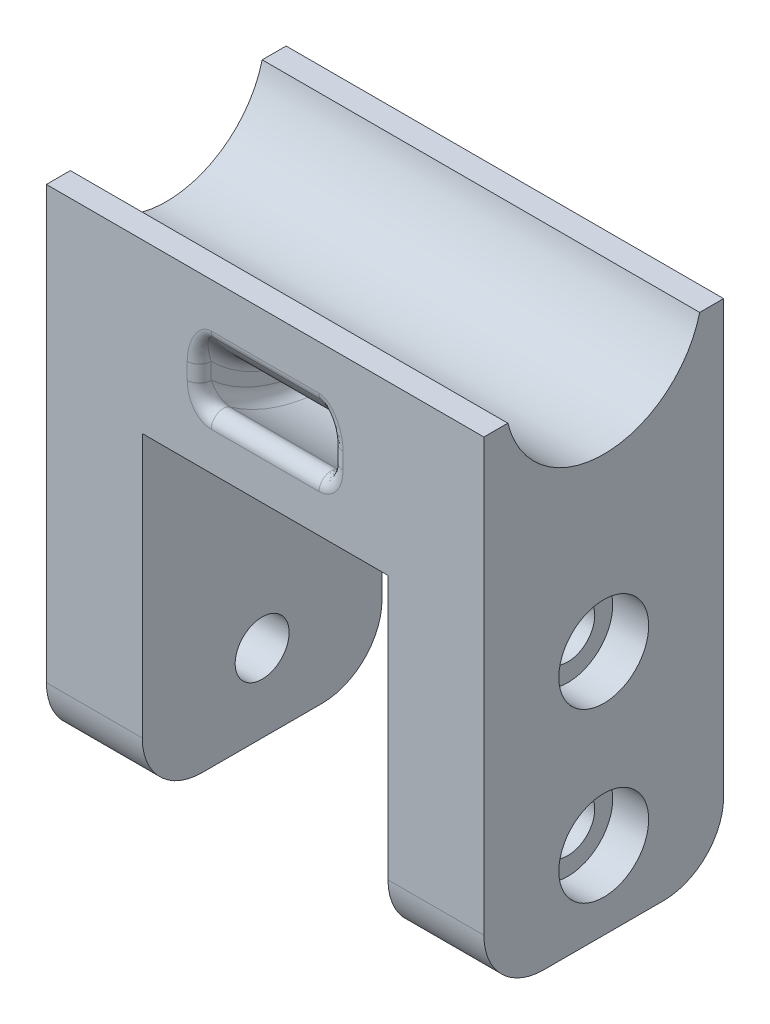
SolidWorks part; units mm, degrees
ref_plane "Спереди" through (0, 0, 0) normal (0, 0, 1) x (1, 0, 0)
ref_plane "Сверху" through (0, 0, 0) normal (0, 1, 0) x (1, 0, 0)
ref_plane "Справа" through (0, 0, 0) normal (1, 0, 0) x (0, 0, -1)
sketch "Эскиз1" plane through (0, 0, 0) normal (0, 1, 0) x (1, 0, 0)
  line L1 (-10, 10) -> (10, 10)
  line L2 (-10, 10) -> (-10, -10)
  line L3 (-10, -10) -> (10, -10)
  line L4 (10, 10) -> (10, -10)
  line L5 (-10, 10) -> (10, -10) construction
  line L6 (-10, -10) -> (10, 10) construction
  point P0 (0, 0)
  dimension "D1" = 20
  dimension "D2" = 20
extrude "Бобышка-Вытянуть1" add sketch "Эскиз1" along normal blind 14
sketch "Эскиз2" plane through (-10, 0, 0) normal (-1, 0, 0) x (0, 0, 1)
  line L0 (-10, 14) -> (10, 14) construction
  circle A0 centre (0, 16) radius 8.25
  dimension "D1" = 16.5
  dimension "D2" = 2
extrude "Вырез-Вытянуть1" cut sketch "Эскиз2" against normal through all
sketch "Эскиз3" plane through (0, 0, 0) normal (1, 0, 0) x (0, 0, -1)
  line L0 (-10, 14) -> (-10, 10) construction
  line L1 (-10, 14) -> (-10, 0) construction
  circle A0 centre (0, 16) radius 11.6619
  circle A1 centre (0, 16) radius 14.6619
  arc A2 (-8.0039, 14) -> (8.0039, 14) centre (0, 16) ccw construction
  dimension "D1" = 4
  dimension "D2" = 3
extrude "Вырез-Вытянуть2" cut sketch "Эскиз3" against normal mid plane 11
fillet "Скругление1" radius 1 12 edges at (0, 5.2775, -10) (5.5, 1.3381, 0) (0, 5.2775, 10) (-5.5, 1.3381, 0) (-5.5, 4.3381, 0) (0, 10, 10) (5.5, 4.3381, 0) (0, 10, -10) (-5.5, 7.6388, 10) (-5.5, 7.6388, -10) (5.5, 7.6388, 10) (5.5, 7.6388, -10)
sketch "Эскиз5" plane through (-10, 0, 0) normal (-1, 0, 0) x (0, 0, 1)
  line L0 (10, 14) -> (10, 0) construction
  line L1 (10, -27) -> (-10, -27)
  line L2 (10, -27) -> (10, 0)
  line L3 (10, 0) -> (-10, 0) construction
  line L4 (-10, -27) -> (-10, 0)
  line L5 (10, -27) -> (-10, 0) construction
  line L6 (10, 0) -> (-10, -27) construction
  line L7 (-10, -13.5) -> (10, -13.5) construction
  line L18 (10, 14) -> (8.0039, 14)
  line L19 (-8.0039, 14) -> (-10, 14)
  line L20 (-10, 14) -> (-10, 0)
  line L21 (-10, 0) -> (10, 0)
  line L22 (10, 0) -> (10, 14)
  line L23 (10, 14) -> (8.0039, 14)
  line L24 (-8.0039, 14) -> (-10, 14)
  line L25 (-10, 14) -> (-10, 0)
  line L26 (-10, 0) -> (10, 0) construction
  line L27 (10, 0) -> (10, 14)
  circle A0 centre (0, -6.5) radius 2.25
  circle A1 centre (0, -20.5) radius 2.25
  arc A4 (-8.0039, 14) -> (8.0039, 14) centre (0, 16) ccw
  arc A5 (-8.0039, 14) -> (8.0039, 14) centre (0, 16) ccw
  point P0 (0, -13.5)
  dimension "D2" = 4.5
  dimension "D1" = 27
  dimension "D3" = 14
  dimension "D4" = 0
extrude "Бобышка-Вытянуть2" add sketch "Эскиз5" along normal blind 8.25
sketch "Эскиз6" plane through (-10, 0, 0) normal (1, 0, 0) x (0, 0, -1)
  line L8 (10, -27) -> (10, 0)
  line L9 (10, 0) -> (-10, 0)
  line L10 (-10, 0) -> (-10, -27)
  line L11 (-10, -27) -> (10, -27)
  line L12 (10, -27) -> (10, 0)
  line L13 (10, 0) -> (-10, 0)
  line L14 (-10, 0) -> (-10, -27)
  line L15 (-10, -27) -> (10, -27)
  dimension "D1" = 0
extrude "Вырез-Вытянуть3" cut sketch "Эскиз6" against normal blind 0.25
sketch "Эскиз7" plane through (-18.25, 0, 0) normal (-1, 0, 0) x (0, 0, 1)
  circle A0 centre (0, -6.5) radius 3.75
  circle A1 centre (0, -20.5) radius 3.75
  dimension "D1" = 7.5
  dimension "D2" = 7.5
extrude "Вырез-Вытянуть4" cut sketch "Эскиз7" against normal blind 3
fillet "Скругление2" radius 5 2 edges at (-14.25, -27, -10) (-14.25, -27, 10)
mirror "Зеркальное отражение1" about plane through (0, 0, 0) normal (1, 0, 0) of "Вырез-Вытянуть3", "Скругление2", "Вырез-Вытянуть4", "Бобышка-Вытянуть2"
equation "\"print_offset\"= 0.5"
equation "\"screw_m5_d\"= 4"
equation "\"screw_m5_hh_d\"= 7"
equation "\"nut_m5_d\"= 7.9"
equation "\"nut_m5_h\"= 3.9"
equation "\"tube_d\"= 16"
equation "\"tube_tape_d\"= 3"
equation "\"tube_tape_h\"= 11"
equation "\"D2@Эскиз1\"=\"D1@Эскиз1\""
equation "\"D1@Эскиз2\"=\"tube_d\"+\"print_offset\""
equation "\"D2@Эскиз3\"=\"tube_tape_d\""
equation "\"D1@Вырез-Вытянуть2\"=\"tube_tape_h\""
equation "\"D2@Эскиз5\"=\"screw_m5_d\"+\"print_offset\""
equation "\"D1@Бобышка-Вытянуть2\"=\"print_offset\"/2+8"
equation "\"D1@Вырез-Вытянуть3\"=\"print_offset\"/2"
equation "\"D1@Эскиз7\"=\"screw_m5_hh_d\"+\"print_offset\""
equation "\"D2@Эскиз7\"=\"D1@Эскиз7\""
